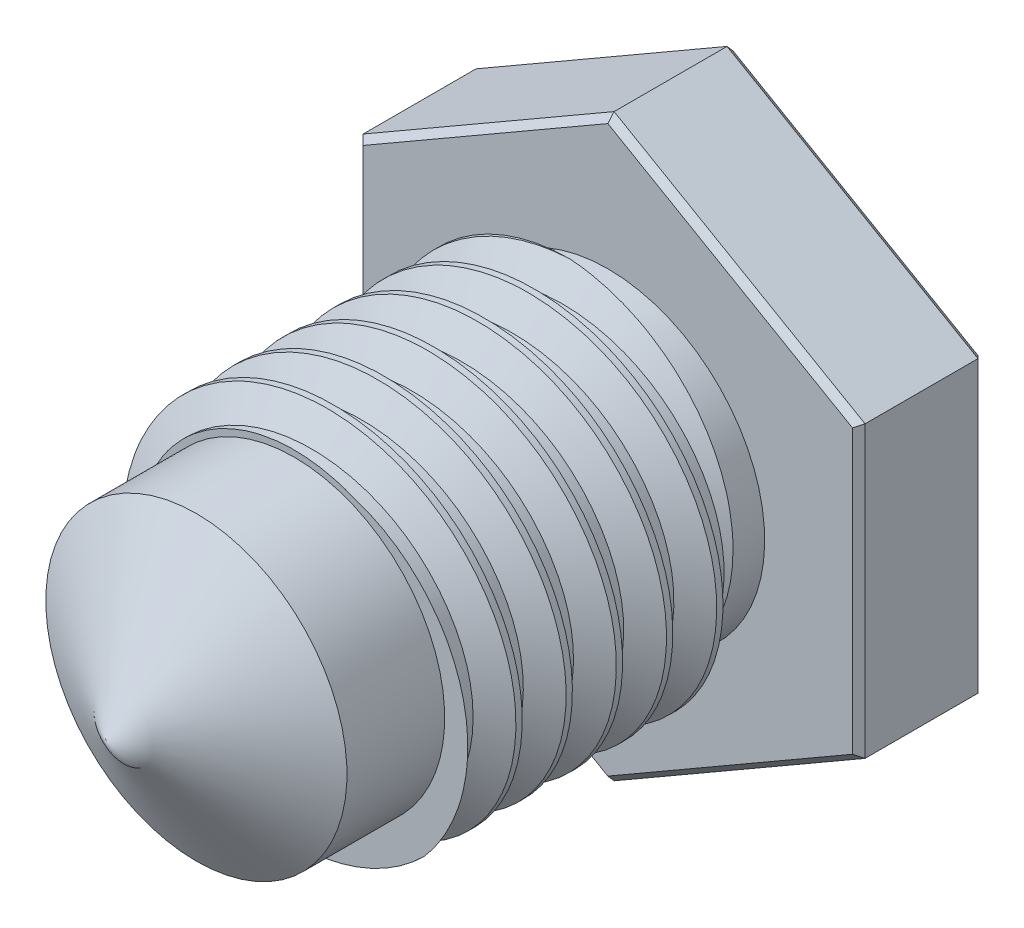
SolidWorks part; units mm, degrees
ref_plane "Front Plane" through (0, 0, 0) normal (0, 0, 1) x (1, 0, 0)
ref_plane "Top Plane" through (0, 0, 0) normal (0, 1, 0) x (1, 0, 0)
ref_plane "Right Plane" through (0, 0, 0) normal (1, 0, 0) x (0, 0, -1)
sketch "Sketch1" plane through (0, 0, 0) normal (1, 0, 0) x (0, 0, -1)
  line L0 (0, 0) -> (-10, 0) construction
  line L2 (-8.2377, 2.933) -> (-2.6, 2.933)
  line L3 (-2, 2.5) -> (-2, 5)
  line L4 (-2, 5) -> (0, 5)
  line L5 (0, 5) -> (0, 0)
  line L6 (0, 0) -> (-10, 0)
  line L7 (-10, 0) -> (-8.2377, 2.933)
  line L8 (-2, 2.5) -> (-2.6, 2.5)
  line L9 (-2.6, 2.5) -> (-2.6, 2.933)
  dimension "D1" = 10
  dimension "D2" = 59
  dimension "D3" = 10
  dimension "D4" = 5.866
  dimension "D5" = 0.6
  dimension "D6" = 5
  dimension "D7" = 2
revolve "Revolve1" add sketch "Sketch1" angle 360 about L0
thread "Thread1" pitch 0.8 profile "Thread Profile1" start angle 0, offset 2.7, length 28, pitch 0.8, diameter 5.866
ref_plane "Plane1" through (-2.933, 0, 2.7) normal (0, -1, 0) x (-1, 0, 0)
sketch "Thread Profile1" plane through (-2.933, 0, 2.7) normal (0, -1, 0) x (-1, 0, 0)
  line L0 (0, 0) -> (0, 0.8) construction
  line L11 (0, 0) -> (0, 0.7)
  line L12 (0, 0.7) -> (-0.433, 0.45)
  line L13 (-0.433, 0.45) -> (-0.433, 0.25)
  line L15 (-0.433, 0.25) -> (0, 0)
  line L17 (-0.433, 0.35) -> (0, 0.35) construction
  point P2 (0, 0)
  dimension "Pitch" = 0.8
  dimension "Profile_Angle" = 60
  dimension "Profile_Land" = 0.2
  dimension "Profile_Height" = 0.433
sketch "Sketch5" plane through (0, 0, 0) normal (0, 0, -1) x (-1, 0, 0)
  line L1 (0, 4.6188) -> (-4, 2.3094)
  line L2 (-4, 2.3094) -> (-4, -2.3094)
  line L3 (-4, -2.3094) -> (0, -4.6188)
  line L4 (0, -4.6188) -> (4, -2.3094)
  line L5 (4, -2.3094) -> (4, 2.3094)
  line L6 (4, 2.3094) -> (0, 4.6188)
  circle A0 centre (0, 0) radius 4 construction
  circle A1 centre (0, 0) radius 5.2104
  dimension "D1" = 8
ref_plane "Plane2" through (0, 0, 10) normal (0, 0, -1) x (-1, 0, 0)
extrude "Cut-Extrude1" cut sketch "Sketch5" against normal blind 10
chamfer "Chamfer1" distance 0.1 angle 45 12 edges at (-2, 3.4641, 2) (-4, 0, 2) (-2, -3.4641, 2) (2, -3.4641, 2) (4, 0, 2) (2, 3.4641, 2) (-2, 3.4641, 0) (-4, 0, 0) (-2, -3.4641, 0) (2, -3.4641, 0) (4, 0, 0) (2, 3.4641, 0)
sketch "Sketch7" plane through (0, 0, 10) normal (0, 0, -1) x (-1, 0, 0)
  circle A0 centre (0, 0) radius 2.4
  circle A1 centre (0, 0) radius 2.933
  dimension "D1" = 4.8
extrude "Cut-Extrude2" cut sketch "Sketch7" along normal blind 3
